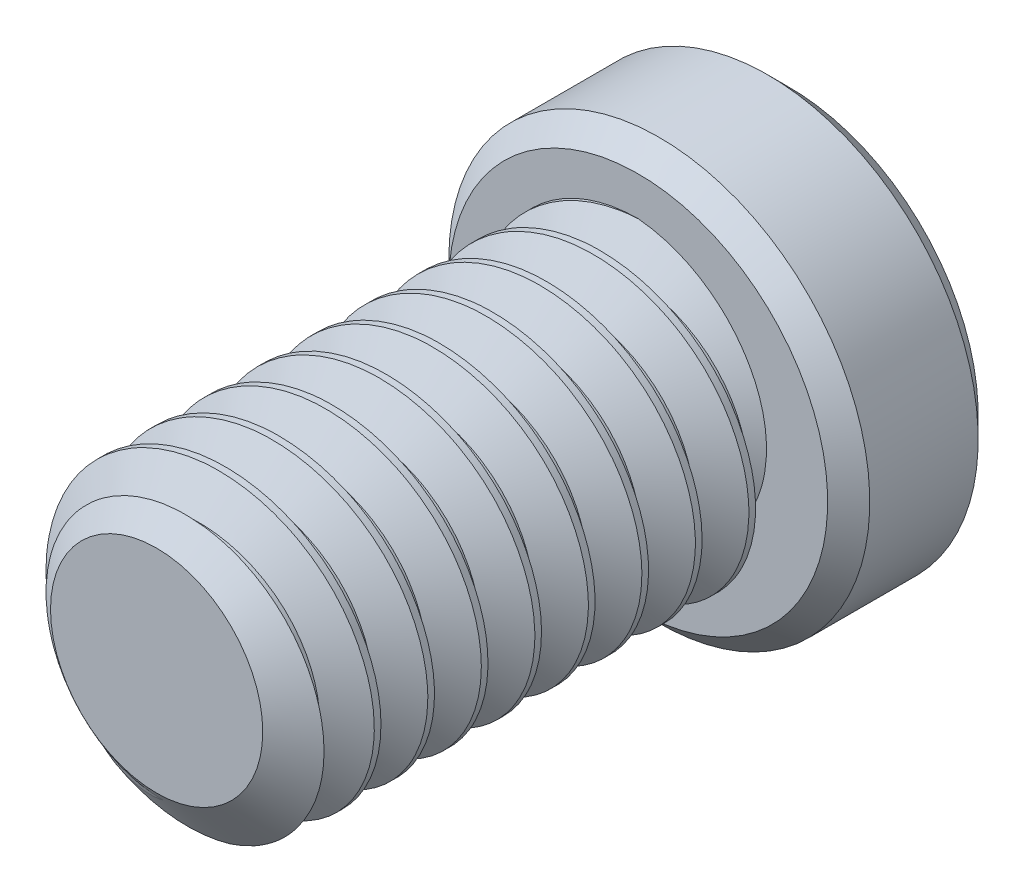
SolidWorks part; units mm, degrees
other "DetailItem1"
ref_plane "Front Plane" through (0, 0, 0) normal (0, 0, 1) x (1, 0, 0)
ref_plane "Top Plane" through (0, 0, 0) normal (0, 1, 0) x (1, 0, 0)
ref_plane "Right Plane" through (0, 0, 0) normal (1, 0, 0) x (0, 0, -1)
sketch "Sketch1" plane through (0, 0, 0) normal (0, 0, 1) x (1, 0, 0)
  circle A0 centre (0, 0) radius 3.9688
  dimension "OD" = 7.9375
extrude "Extrude1" add sketch "Sketch1" against normal blind 12.7
sketch "Sketch2" plane through (0, 0, 0) normal (0, 0, 1) x (1, 0, 0)
  circle A0 centre (0, 0) radius 3.9688 construction
  circle A1 centre (0, 0) radius 3.9688
curve "Helix/Spiral1" pitch 1.4111 height 14.1111 turns 10 parameters "pitch"=1.4111
sketch "Sketch3" plane through (0, 0, 0) normal (1, 0, 0) x (0, 0, -1)
  line L0 (-1.2347, 3.9688) -> (-0.7056, 3.0522)
  line L1 (-0.7056, 3.0522) -> (-0.5292, 3.0522)
  line L2 (-0.5292, 3.0522) -> (0, 3.9688)
  line L3 (-1.2347, 3.9688) -> (0, 3.9688)
  line L4 (-0.6174, 3.9688) -> (-0.6174, 3.0522) construction
  line L5 (-0.9701, 3.5105) -> (-0.2646, 3.5105) construction
  line L6 (0, 3.9688) -> (0, -3.9688) construction
  dimension "D1" = 0.1764
  dimension "D2" = 0.7056
  dimension "D3" = 60
sweep "Cut-Sweep1" cut profiles "Sketch3" path "Helix/Spiral1"
sketch "Sketch4" plane through (0, 0, 0) normal (1, 0, 0) x (0, 0, -1)
  line L0 (0.8196, 3.9688) -> (0, 2.7982)
  line L1 (0, 2.7982) -> (0, 3.9688)
  line L2 (0.8196, 3.9688) -> (0, 3.9688)
  line L3 (-1.2347, 3.9688) -> (0, 3.9688) construction
  line L4 (0, 0) -> (7.0209, 0) construction
  dimension "D1" = 55
  dimension "D2" = 0.254
revolve "Cut-Revolve1" cut sketch "Sketch4" angle 360 about L4
sketch "Sketch6" plane through (0, 0, -12.7) normal (0, 0, -1) x (-1, 0, 0)
  circle A0 centre (0, 0) radius 5.5499
  dimension "head dia" = 11.0998
extrude "Extrude2" add sketch "Sketch6" along normal blind 3.9688
sketch "Sketch7" plane through (0, 0, -16.6687) normal (0, 0, -1) x (-1, 0, 0)
  line L1 (0, 2.2914) -> (-1.9844, 1.1457)
  line L2 (-1.9844, 1.1457) -> (-1.9844, -1.1457)
  line L3 (-1.9844, -1.1457) -> (0, -2.2914)
  line L4 (0, -2.2914) -> (1.9844, -1.1457)
  line L5 (1.9844, -1.1457) -> (1.9844, 1.1457)
  line L6 (1.9844, 1.1457) -> (0, 2.2914)
  circle A0 centre (0, 0) radius 1.9844 construction
  dimension "hex dia" = 3.9688
extrude "Cut-Extrude1" cut sketch "Sketch7" against normal blind 2.9766
sketch "Sketch8" plane through (0, 0, -16.6687) normal (0, 0, -1) x (-1, 0, 0)
  circle A0 centre (0, 0) radius 2.2914
extrude "Cut-Extrude2" cut sketch "Sketch8" against normal through all draft 45
chamfer "Chamfer1" distance 0.555 angle 45 2 edges at (-5.5499, 0, -16.6687) (-5.5499, 0, -12.7)
sketch "Sketch10" plane through (0, 0, -12.7) normal (0, 0, 1) x (1, 0, 0)
  circle A1 centre (0, 0) radius 3.9688
  circle A2 centre (0, 0) radius 3.9688
  dimension "D1" = 0
ref_plane "Plane1" through (0, 0, -38.1) normal (0, 0, 1) x (1, 0, 0)
extrude "partial thread" [suppressed] add sketch "Sketch10" along normal up to surface (12.7 mm away) separate body
chamfer "Chamfer2" [suppressed] distance 0.1588 angle 45
combine bodies "Combine1" [suppressed] operation type add bodies to combine 107 108
sketch "Sketch9" plane through (0, 0, 0) normal (1, 0, 0) x (0, 0, -1)
  line L0 (0, 3.9688) -> (0, -3.9688) construction
  line L1 (3.5278, 3.9688) -> (3.5278, -3.9688) construction
  dimension "D1" = 3.5278
equation "\"D3@Helix/Spiral1\" = \"screw length@Extrude1\"+\"pitch@Helix/Spiral1\""
equation "\"D1@Sketch3\" = \"pitch@Helix/Spiral1\"*.125"
equation "\"D2@Sketch3\" = \"pitch@Helix/Spiral1\"*.5"
equation "\"D1@Cut-Extrude1\" = \"hex dia@Sketch7\"*.75"
equation "\"D1@Chamfer1\" = \"head dia@Sketch6\"*.05"
equation "\"D1@Sketch9\" = \"pitch@Helix/Spiral1\"*2.5"
equation "\"D1@Chamfer2\"=\"OD@Sketch1\"*.02"
